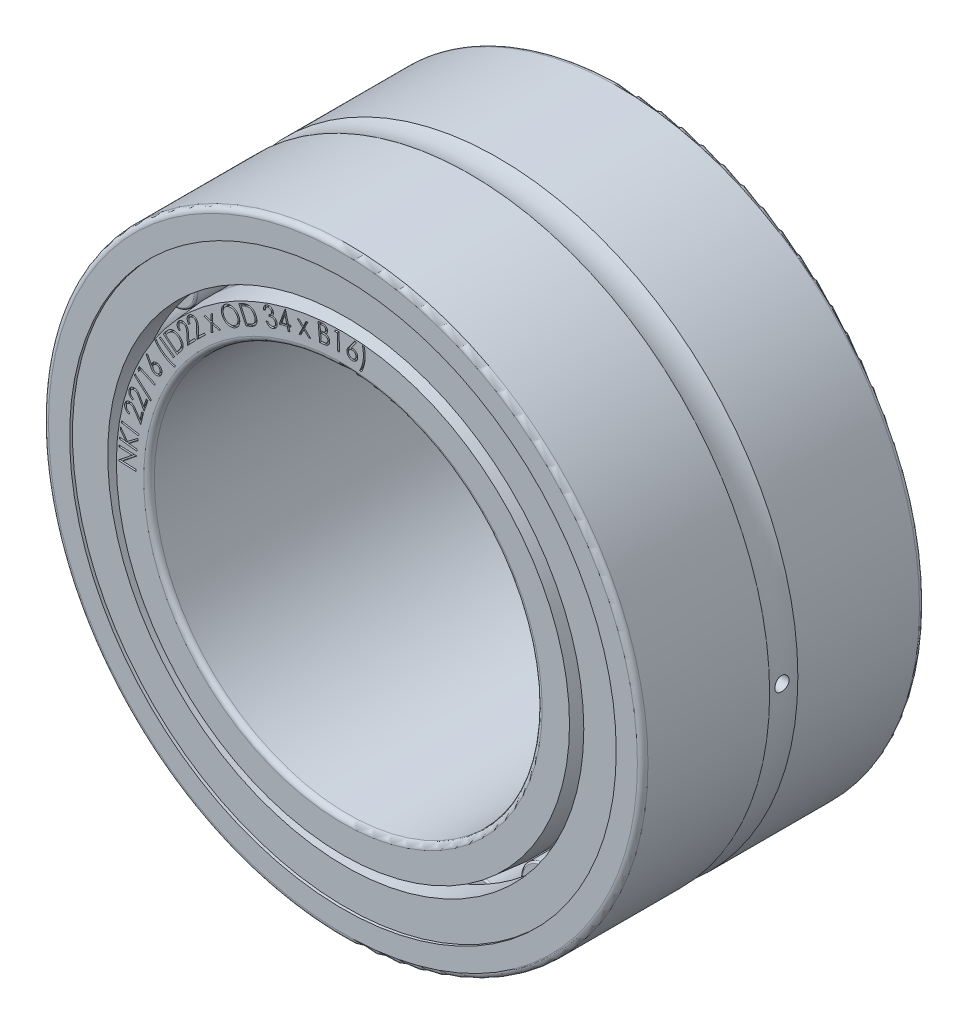
SolidWorks part; units mm, degrees
material "CS1020"
ref_plane "Front Plane" through (0, 0, 0) normal (0, 0, 1) x (1, 0, 0)
ref_plane "Top Plane" through (0, 0, 0) normal (0, 1, 0) x (1, 0, 0)
ref_plane "Right Plane" through (0, 0, 0) normal (1, 0, 0) x (0, 0, -1)
sketch "Sketch2" plane through (0, 0, 0) normal (1, 0, 0) x (0, 0, -1)
  line L0 (0, 0) -> (14.7851, 0) construction
  line L1 (0, 0) -> (0, 22) construction
  line L2 (-7.7, 17) -> (-0.8, 17)
  line L3 (8, 16.7) -> (8, 15.5)
  line L4 (7.84, 13.5) -> (6.4, 13.5)
  line L5 (7.84, 15.5) -> (7.84, 13.5)
  line L6 (6.4, 15.5) -> (6.4, 13.5)
  line L7 (8, 12.85) -> (8, 11.3)
  line L8 (7.7, 11) -> (-7.7, 11)
  line L9 (-8, 12.85) -> (-8, 11.3)
  line L10 (-8, 12.85) -> (-6.4, 13)
  line L11 (-7.84, 15.5) -> (-7.84, 13.5)
  line L12 (-8, 15.5) -> (-7.84, 15.5)
  line L13 (-8, 16.7) -> (-8, 15.5)
  line L14 (-7.84, 13.5) -> (-6.4, 13.5)
  line L15 (0.8, 17) -> (7.7, 17)
  line L16 (7.84, 15.5) -> (8, 15.5)
  line L17 (-6.4, 15.5) -> (6.4, 15.5)
  line L18 (-6.4, 15.5) -> (-6.4, 13.5)
  line L19 (-6.4, 13) -> (6.4, 13)
  line L20 (8, 12.85) -> (6.4, 13)
  arc A0 (-0.8, 17) -> (0.8, 17) centre (0, 19.3685) ccw
  arc A1 (7.7, 17) -> (8, 16.7) centre (7.7, 16.7) cw
  arc A2 (8, 11.3) -> (7.7, 11) centre (7.7, 11.3) cw
  arc A3 (-8, 11.3) -> (-7.7, 11) centre (-7.7, 11.3) ccw
  arc A4 (-8, 16.7) -> (-7.7, 17) centre (-7.7, 16.7) cw
  point P13 (0, 11)
  point P18 (0, 27.5)
  point P28 (8, 17)
  point P32 (8, 11)
  point P35 (-8, 11)
  point P38 (-8, 17)
  dimension "D1" = 5
  dimension "D8" = 1.6
  dimension "D14" = 0.3
  dimension "D2" = 16
  dimension "D3" = 22
  dimension "D4" = 0.16
  dimension "D5" = 34
  dimension "D6" = 31
  dimension "D7" = 27
  dimension "D9" = 31
  dimension "D10" = 12.8
  dimension "D11" = 1.6
  dimension "D12" = 26
  dimension "D13" = 25.7
revolve "Revolve1" add sketch "Sketch2" angle 360 about L0
sketch "Sketch4" plane through (0, 0, 8) normal (0, 0, -1) x (-1, 0, 0)
  circle A0 centre (0, 0) radius 11.75 construction
  text T0 "NKI 22/16 (ID22 x OD 34 x B16)" font "Century Gothic" height 1
  dimension "D1" = 23.5
extrude "Extrude4" cut sketch "Sketch4" along normal blind 0.1
sketch "Sketch5" plane through (0, 0, 0) normal (0, 1, 0) x (1, 0, 0)
  line L0 (0, 0) -> (21.141, 0) construction
  line L2 (12.5768, 0) -> (19.1279, 0)
  line L3 (12.5768, 0) -> (12.5768, 0.4)
  line L4 (12.5768, 0.4) -> (19.1279, 0.4)
  line L5 (19.1279, 0) -> (19.1279, 0.4)
  dimension "D1" = 0.8
  dimension "D2" = 12.5768
  dimension "D3" = 6.5511
revolve "Cut-Revolve1" cut sketch "Sketch5" angle 360 about L0
sketch "Sketch6" plane through (0, 0, 0) normal (1, 0, 0) x (0, 0, -1)
  line L0 (-10.861, 14.3) -> (10.5329, 14.3) construction
  line L1 (-6.4, -13.5) -> (-6.4, 13.5) construction
  line L2 (-6.4, 14.3) -> (6.4, 14.3)
  line L3 (-6.4, 14.3) -> (-6.4, 15.45)
  line L4 (-6.3, 15.55) -> (6.3, 15.55)
  line L5 (6.4, 14.3) -> (6.4, 15.45)
  arc A0 (6.3, 15.55) -> (6.4, 15.45) centre (6.3, 15.45) cw
  arc A1 (-6.4, 15.45) -> (-6.3, 15.55) centre (-6.3, 15.45) cw
  dimension "D4" = 0.1
  dimension "D1" = 2.5
  dimension "D2" = 12.8
  dimension "D3" = 14.3
revolve "Revolve2" add sketch "Sketch6" angle 360 about L0
pattern_circular "CirPattern1" count 21 over 360 about axis through (0, 0, 0) along (0, 0, 1) of "Revolve2"
